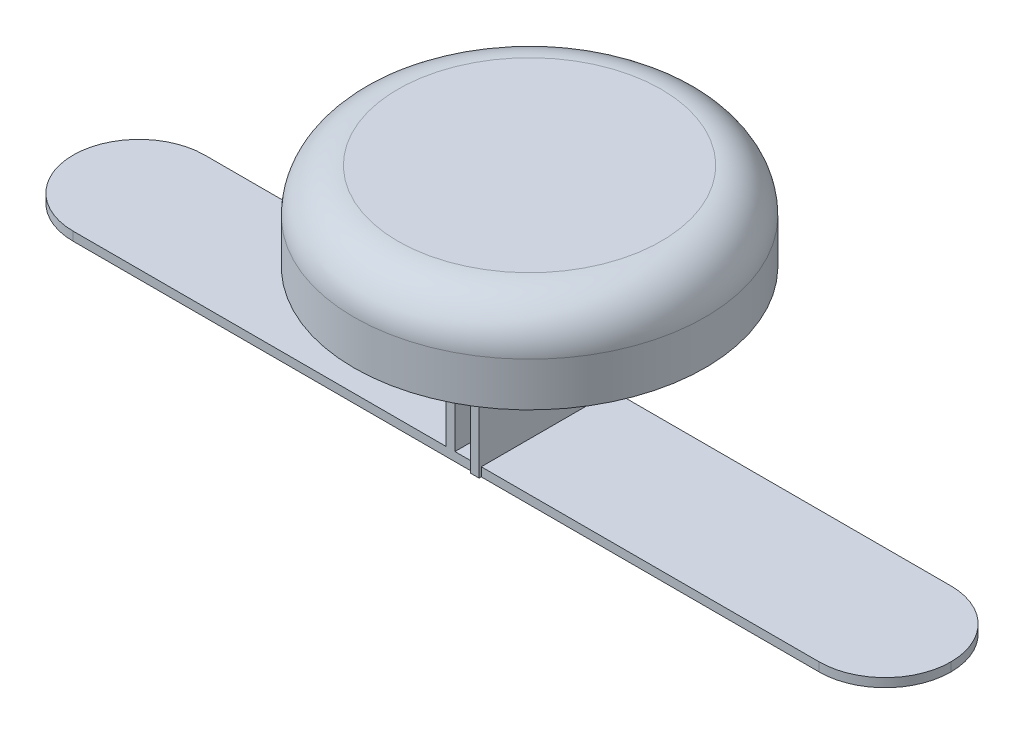
SolidWorks part; units mm, degrees
ref_plane "Plan de face" through (0, 0, 0) normal (0, 0, 1) x (1, 0, 0)
ref_plane "Plan de dessus" through (0, 0, 0) normal (0, 1, 0) x (1, 0, 0)
ref_plane "Plan de droite" through (0, 0, 0) normal (1, 0, 0) x (0, 0, -1)
sketch "Esquisse1" plane through (0, 0, 0) normal (0, 1, 0) x (1, 0, 0)
  circle A0 centre (0, 0) radius 4
  dimension "D1" = 8
extrude "Boss.-Extru.1" add sketch "Esquisse1" along normal blind 2
fillet "Congé1" radius 1 1 edges at (0, 2, 4)
sketch "Esquisse2" plane through (0, 0, 0) normal (0, -1, 0) x (1, 0, 0)
  line L1 (-0.4, 1.5) -> (-0.2, 1.5)
  line L2 (-0.4, 1.5) -> (-0.4, -1.5)
  line L3 (-0.4, -1.5) -> (-0.2, -1.5)
  line L4 (-0.2, 1.5) -> (-0.2, -1.5)
  line L5 (0.2, 1.55) -> (0.4, 1.55)
  line L6 (0.2, 1.55) -> (0.2, -1.45)
  line L7 (0.2, -1.45) -> (0.4, -1.45)
  line L8 (0.4, 1.55) -> (0.4, -1.45)
  dimension "D1" = 3
  dimension "D2" = 3
  dimension "D3" = 1.55
  dimension "D4" = 1.5
  dimension "D5" = 0.2
  dimension "D6" = 0.2
  dimension "D7" = 0.2
  dimension "D8" = 0.2
extrude "Boss.-Extru.2" add sketch "Esquisse2" along normal blind 3.2
sketch "Esquisse3" plane through (-0.4, 0, 0) normal (-1, 0, 0) x (0, 0, 1)
  line L0 (1.5, -3.2) -> (1.5, 0) construction
  line L1 (1.5, -3) -> (-1.5, -3)
  line L2 (1.5, -3) -> (1.5, -3.2)
  line L3 (1.5, -3.2) -> (-1.5, -3.2)
  line L4 (-1.5, -3) -> (-1.5, -3.2)
  line L5 (-1.5, -3.2) -> (-1.5, 0) construction
  line L6 (1.5, 0) -> (-1.5, 0) construction
  dimension "D1" = 0.2
  dimension "D2" = 3
extrude "Boss.-Extru.3" add sketch "Esquisse3" along normal blind 10 and the other way blind 10
fillet "Congé2" radius 1.5 4 edges at (-10.4, -3.1, 1.5) (-10.4, -3.1, -1.5) (9.6, -3.1, 1.5) (9.6, -3.1, -1.5)
